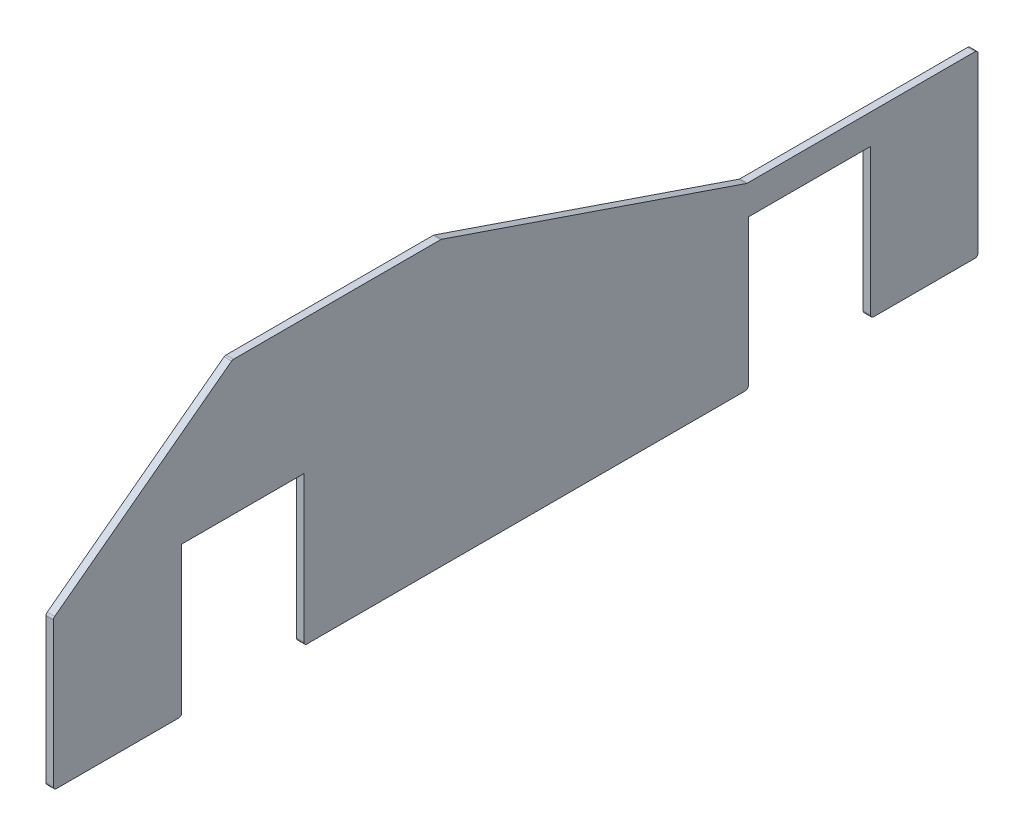
SolidWorks part; units mm, degrees
ref_plane "前视基准面" through (0, 0, 0) normal (0, 0, 1) x (1, 0, 0)
ref_plane "上视基准面" through (0, 0, 0) normal (0, 1, 0) x (1, 0, 0)
ref_plane "右视基准面" through (0, 0, 0) normal (1, 0, 0) x (0, 0, -1)
sketch "Sketch1" plane through (0, 0, 0) normal (1, 0, 0) x (0, 0, -1)
  line L1 (-310, -95) -> (310, -95)
  line L2 (-310, -95) -> (-310, 95)
  line L3 (-310, 95) -> (310, 95)
  line L4 (310, -95) -> (310, 95)
  line L5 (-310, -95) -> (310, 95) construction
  line L6 (-310, 95) -> (310, -95) construction
  point P0 (0, 0)
  dimension "D1" = 620
  dimension "D2" = 190
extrude "Boss-Extrude1" add sketch "Sketch1" along normal blind 5
sketch "Sketch2" plane through (5, 0, 0) normal (1, 0, 0) x (0, 0, -1)
  line L0 (-310, -95) -> (310, -95) construction
  line L1 (-224, -95) -> (-142, -95)
  line L2 (-224, -95) -> (-224, 5)
  line L3 (-224, 5) -> (-142, 5)
  line L4 (-142, -95) -> (-142, 5)
  line L5 (-310, 95) -> (-310, -95) construction
  line L6 (156, -95) -> (238, -95)
  line L7 (156, -95) -> (156, 5)
  line L8 (156, 5) -> (238, 5)
  line L9 (238, -95) -> (238, 5)
  line L10 (310, -95) -> (310, 95) construction
  line L11 (-310, 5) -> (-190, 95)
  line L12 (310, 95) -> (-310, 95) construction
  line L13 (-50, 95) -> (155, 25)
  line L14 (155, 25) -> (310, 25)
  point P21 (310, 25)
  line M9 (310, -95) -> (310, 95)
  line M10 (310, 95) -> (-310, 95)
  line M11 (-310, 95) -> (-310, -95)
  line M12 (-310, -95) -> (310, -95)
  dimension "D1" = 100
  dimension "D2" = 100
  dimension "D3" = 82
  dimension "D4" = 82
  dimension "D5" = 86
  dimension "D6" = 72
  dimension "D7" = 360
  dimension "D8" = 20
  dimension "D9" = 155
  dimension "D10" = 100
  dimension "D11" = 120
extrude "Cut-Extrude1" cut sketch "Sketch2" against normal blind 5 contours L11 M11 M10 | L13 L14 M9 M10 | L4 L3 L2 M12 | L9 L8 L7 M12 region at (5, -45, 183) region at (5, -45, -197) region at (5, 65, 270) region at (5, 64.644, -174.4498)
fillet "Fillet1" radius 2 11 edges at (2.5, 95, 50) (2.5, 5, 310) (2.5, -95, 310) (2.5, -95, 224) (2.5, -95, 142) (2.5, -95, -156) (2.5, -95, -238) (2.5, -95, -310) (2.5, 25, -310) (2.5, 25, -155) (2.5, 95, 190)
